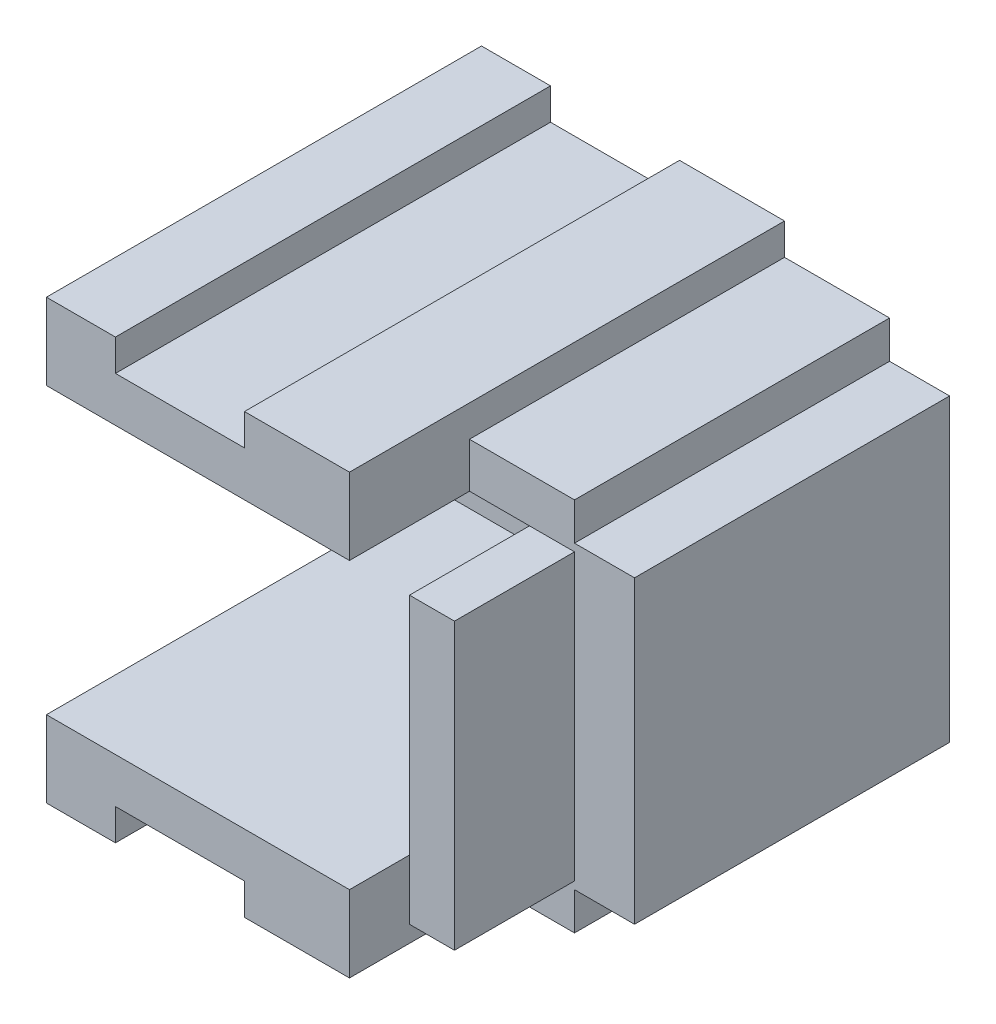
SolidWorks part; units mm, degrees
ref_plane "Front Plane" through (0, 0, 0) normal (1, 0, 0) x (0, 1, 0)
ref_plane "Top Plane" through (0, 0, 0) normal (0, 0, 1) x (0, 1, 0)
ref_plane "Right Plane" through (0, 0, 0) normal (0, 1, 0) x (-1, 0, 0)
sketch "Sketch2" plane through (0, 0, 0) normal (1, 0, 0) x (0, 1, 0)
  line L1 (5, 5.25) -> (-5, 5.25)
  line L2 (5, 5.25) -> (5, -5.25)
  line L3 (5, -5.25) -> (-5, -5.25)
  line L4 (-5, 5.25) -> (-5, -5.25)
  line L5 (5, 5.25) -> (-5, -5.25) construction
  line L6 (5, -5.25) -> (-5, 5.25) construction
  point P0 (0, 0)
  dimension "D1" = 10.5
  dimension "D2" = 10
extrude "Boss-Extrude1" add sketch "Sketch2" along normal blind 2
sketch "Sketch3" plane through (0, 0, 0) normal (-1, 0, 0) x (0, -1, 0)
  line L1 (-6.25, -5.25) -> (6.25, -5.25)
  line L2 (-6.25, -5.25) -> (-6.25, 9.25)
  line L3 (-6.25, 9.25) -> (6.25, 9.25)
  line L4 (5, -5.25) -> (5, 5.25)
  line L5 (5, 5.25) -> (-5, 5.25)
  line L6 (-5, 5.25) -> (-5, -5.25)
  line L7 (-5, -5.25) -> (5, -5.25)
  line L8 (5, -5.25) -> (5, 5.25) construction
  line L9 (5, 5.25) -> (-5, 5.25) construction
  line L10 (-5, 5.25) -> (-5, -5.25) construction
  line L11 (-5, -5.25) -> (5, -5.25) construction
  line L12 (6.25, -5.25) -> (6.25, 9.25)
  point P8 (0, -5.25)
  point P9 (0, -5.25)
  dimension "D2" = 12.5
  dimension "D3" = 14.5
  dimension "D1" = 0
extrude "Boss-Extrude2" add sketch "Sketch3" along normal blind 3.5
sketch "Sketch4" plane through (-3.5, 0, 0) normal (-1, 0, 0) x (0, -1, 0)
  line L1 (-7.3, -5.25) -> (7.3, -5.25)
  line L2 (-7.3, -5.25) -> (-7.3, 9.25)
  line L3 (-7.3, 9.25) -> (7.3, 9.25)
  line L4 (-6.25, 9.25) -> (-6.25, -5.25)
  line L5 (-6.25, -5.25) -> (6.25, -5.25)
  line L6 (6.25, -5.25) -> (6.25, 9.25)
  line L7 (6.25, 9.25) -> (-6.25, 9.25)
  line L8 (-6.25, 9.25) -> (-6.25, -5.25) construction
  line L9 (-6.25, -5.25) -> (6.25, -5.25) construction
  line L10 (6.25, -5.25) -> (6.25, 9.25) construction
  line L11 (6.25, 9.25) -> (-6.25, 9.25) construction
  line L12 (7.3, -5.25) -> (7.3, 9.25)
  point P9 (0, -5.25)
  point P10 (0, -5.25)
  dimension "D2" = 14.6
  dimension "D1" = 0
extrude "Boss-Extrude3" add sketch "Sketch4" along normal blind 3.5
sketch "Sketch5" plane through (-7, 0, 0) normal (-1, 0, 0) x (0, -1, 0)
  line L1 (-6.25, -5.25) -> (6.25, -5.25)
  line L2 (-6.25, -5.25) -> (-6.25, 9.25)
  line L3 (-6.25, 9.25) -> (6.25, 9.25)
  line L4 (-7.3, 9.25) -> (-7.3, -5.25)
  line L5 (-7.3, -5.25) -> (7.3, -5.25)
  line L6 (7.3, -5.25) -> (7.3, 9.25)
  line L7 (7.3, 9.25) -> (-7.3, 9.25)
  line L8 (-7.3, 9.25) -> (-7.3, -5.25) construction
  line L9 (-7.3, -5.25) -> (7.3, -5.25) construction
  line L10 (7.3, -5.25) -> (7.3, 9.25) construction
  line L11 (7.3, 9.25) -> (-7.3, 9.25) construction
  line L12 (6.25, -5.25) -> (6.25, 9.25)
  point P8 (0, -5.25)
  point P9 (0, -5.25)
  dimension "D2" = 12.5
  dimension "D1" = 0
extrude "Boss-Extrude4" add sketch "Sketch5" along normal blind 4.3
sketch "Sketch6" plane through (-11.3, 0, 0) normal (-1, 0, 0) x (0, -1, 0)
  line L0 (6.25, 9.25) -> (6.25, -5.25) construction
  line L1 (6.25, -5.25) -> (7.3, -5.25) construction
  line L2 (7.3, -5.25) -> (7.3, 9.25) construction
  line L3 (7.3, 9.25) -> (6.25, 9.25) construction
  line L4 (-6.25, 9.25) -> (-6.25, -5.25) construction
  line L5 (-6.25, -5.25) -> (6.25, -5.25) construction
  line L6 (6.25, -5.25) -> (6.25, 9.25) construction
  line L7 (6.25, 9.25) -> (-6.25, 9.25) construction
  line L8 (-6.25, -5.25) -> (-6.25, 9.25) construction
  line L9 (-6.25, 9.25) -> (-7.3, 9.25) construction
  line L10 (-7.3, 9.25) -> (-7.3, -5.25) construction
  line L11 (-7.3, -5.25) -> (-6.25, -5.25) construction
  line L12 (6.25, 9.25) -> (6.25, -5.25) construction
  line L13 (6.25, -5.25) -> (7.3, -5.25)
  line L14 (7.3, -5.25) -> (7.3, 9.25)
  line L15 (7.3, 9.25) -> (6.25, 9.25)
  line L16 (-6.25, 9.25) -> (-6.25, -5.25) construction
  line L17 (-6.25, -5.25) -> (6.25, -5.25)
  line L18 (6.25, -5.25) -> (6.25, 9.25) construction
  line L19 (6.25, 9.25) -> (-6.25, 9.25)
  line L20 (-6.25, -5.25) -> (-6.25, 9.25) construction
  line L21 (-6.25, 9.25) -> (-7.3, 9.25)
  line L22 (-7.3, 9.25) -> (-7.3, -5.25)
  line L23 (-7.3, -5.25) -> (-6.25, -5.25)
extrude "Boss-Extrude5" add sketch "Sketch6" along normal blind 2.3
sketch "Sketch8" plane through (0, 0, 9.25) normal (0, 0, 1) x (1, 0, 0)
  line L1 (-13.6, 4.75) -> (-1.5, 4.75)
  line L2 (-13.6, 4.75) -> (-13.6, -4.75)
  line L3 (-13.6, -4.75) -> (-1.5, -4.75)
  line L4 (-1.5, 4.75) -> (-1.5, -4.75)
  line L16 (0, -6.25) -> (0, 6.25)
  line L17 (0, 6.25) -> (-3.5, 6.25)
  line L18 (-3.5, 6.25) -> (-3.5, 7.3)
  line L19 (-3.5, 7.3) -> (-7, 7.3)
  line L20 (-7, 7.3) -> (-7, 6.25)
  line L21 (-7, 6.25) -> (-11.3, 6.25)
  line L22 (-11.3, 6.25) -> (-11.3, 7.3)
  line L23 (-11.3, 7.3) -> (-13.6, 7.3)
  line L24 (-13.6, 7.3) -> (-13.6, -7.3)
  line L25 (-13.6, -7.3) -> (-11.3, -7.3)
  line L26 (-11.3, -7.3) -> (-11.3, -6.25)
  line L27 (-11.3, -6.25) -> (-7, -6.25)
  line L28 (-7, -6.25) -> (-7, -7.3)
  line L29 (-7, -7.3) -> (-3.5, -7.3)
  line L30 (-3.5, -7.3) -> (-3.5, -6.25)
  line L31 (-3.5, -6.25) -> (0, -6.25)
  line L32 (0, -6.25) -> (0, 6.25) construction
  line L33 (0, 6.25) -> (-3.5, 6.25) construction
  line L34 (-3.5, 6.25) -> (-3.5, 7.3) construction
  line L35 (-3.5, 7.3) -> (-7, 7.3) construction
  line L36 (-7, 7.3) -> (-7, 6.25) construction
  line L37 (-7, 6.25) -> (-11.3, 6.25) construction
  line L38 (-11.3, 6.25) -> (-11.3, 7.3) construction
  line L39 (-11.3, 7.3) -> (-13.6, 7.3) construction
  line L40 (-13.6, 7.3) -> (-13.6, -7.3) construction
  line L41 (-13.6, -7.3) -> (-11.3, -7.3) construction
  line L42 (-11.3, -7.3) -> (-11.3, -6.25) construction
  line L43 (-11.3, -6.25) -> (-7, -6.25) construction
  line L44 (-7, -6.25) -> (-7, -7.3) construction
  line L45 (-7, -7.3) -> (-3.5, -7.3) construction
  line L46 (-3.5, -7.3) -> (-3.5, -6.25) construction
  line L47 (-3.5, -6.25) -> (0, -6.25) construction
  point P10 (-13.6, 0)
  point P12 (-13.6, 0)
  dimension "D2" = 1.5
  dimension "D3" = 1.5
  dimension "D1" = 0
extrude "Cut-Extrude1" cut sketch "Sketch8" against normal blind 13
sketch "Sketch10" plane through (0, 0, 9.25) normal (0, 0, 1) x (1, 0, 0)
  line L0 (-1.5, 4.75) -> (-13.6, 4.75) construction
  line L9 (0, 6.25) -> (-3.5, 6.25)
  line L10 (0, 6.25) -> (0, 4.75)
  line L11 (0, 4.75) -> (-3.5, 4.75)
  line L12 (-3.5, 6.25) -> (-3.5, 4.75)
  line L13 (-13.6, -4.75) -> (-1.5, -4.75) construction
  line L14 (0, -6.25) -> (-3.5, -6.25)
  line L15 (0, -6.25) -> (0, -4.75)
  line L16 (0, -4.75) -> (-3.5, -4.75)
  line L17 (-3.5, -6.25) -> (-3.5, -4.75)
extrude "Cut-Extrude6" cut sketch "Sketch10" against normal up to surface (4 mm away) up to face at (1, 0, 5.25)
